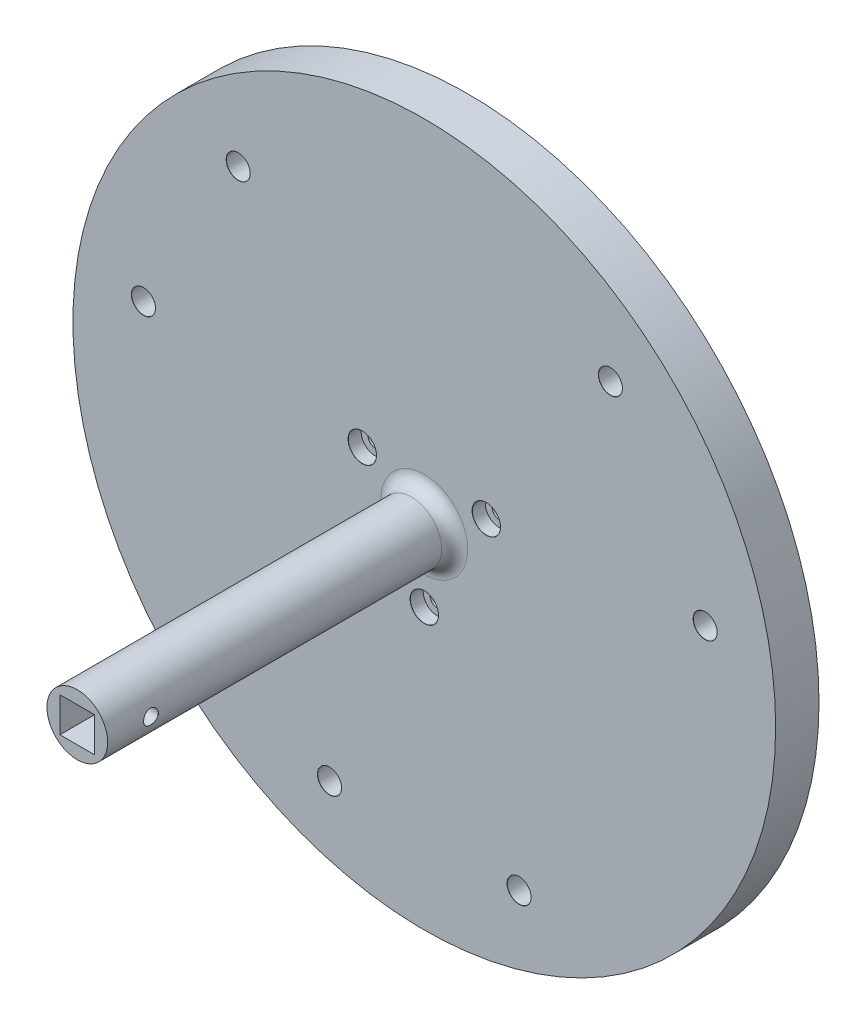
SolidWorks part; units mm, degrees
ref_plane "Front Plane" through (0, 0, 0) normal (0, 0, 1) x (1, 0, 0)
ref_plane "Top Plane" through (0, 0, 0) normal (0, 1, 0) x (1, 0, 0)
ref_plane "Right Plane" through (0, 0, 0) normal (1, 0, 0) x (0, 0, -1)
sketch "Sketch1" plane through (0, 0, 0) normal (0, 0, 1) x (1, 0, 0)
  circle A0 centre (0, 0) radius 81
  dimension "D1" = 162
extrude "Boss-Extrude1" add sketch "Sketch1" along normal blind 10
sketch "Sketch14" plane through (0, 0, 10) normal (0, 0, 1) x (1, 0, 0)
ref_axis "Axis2" through (0, 0, 38.9853) along (0, 0, -1)
sketch "Sketch2" plane through (0, 0, 10) normal (0, 0, 1) x (1, 0, 0)
  line L0 (0, 0) -> (0, -16.51) construction
  line L1 (-14.2981, 8.255) -> (0, 0) construction
  line L2 (0, 0) -> (14.2981, 8.255) construction
  circle A0 centre (0, 0) radius 16.51 construction
  point P7 (-14.2981, 8.255)
  point P8 (14.2981, 8.255)
  point P9 (0, -16.51)
  dimension "D1" = 16.51
  dimension "D2" = 120
  dimension "D3" = 120
sketch "Sketch5" plane through (0, 0, 10) normal (0, 0, 1) x (1, 0, 0)
  point P0 (-14.2981, 8.255)
  point P3 (14.2981, 8.255)
  point P6 (0, -16.51)
hole_wizard "CBORE for M3 SHCS1" positions "Sketch5" profile "Sketch4" counterbore size "M3" standard "ANSI Metric" end condition up to next
sketch "Sketch4" plane through (-14.2981, 8.255, 10) normal (1, 0, 0) x (0, -1, 0)
  line L0 (0, 0) -> (0, 10)
  line L1 (0, 10) -> (1.7, 10)
  line L3 (1.7, 10) -> (1.7, 3)
  line L4 (3.25, 3) -> (1.7, 3)
  line L5 (3.25, 3) -> (3.25, 0.025)
  line L6 (3.25, 0.025) -> (3.275, 0)
  line L7 (3.275, 0) -> (0, 0)
  line L8 (-3.25, 0.025) -> (-3.275, 0) construction
  line L11 (0, -6.35) -> (0, 107.95) construction
  dimension "Thru Hole Dia." = 3.4
  dimension "Thru Hole Depth" = 10
  dimension "C'Bore Dia." = 6.5
  dimension "C'Bore Depth" = 3
  dimension "Near C'Sink Dia." = 6.55
  dimension "Near C'Sink Angle" = 90
sketch "Sketch6" plane through (0, 0, 10) normal (0, 0, 1) x (1, 0, 0)
  circle A0 centre (0, 0) radius 7
  dimension "D1" = 14
extrude "Boss-Extrude2" add sketch "Sketch6" along normal blind 80
sketch "Sketch20" plane through (0, 0, 90) normal (0, 0, 1) x (1, 0, 0)
  line L1 (-4, 4) -> (4, 4)
  line L2 (-4, 4) -> (-4, -4)
  line L3 (-4, -4) -> (4, -4)
  line L4 (4, 4) -> (4, -4)
  line L5 (-4, 4) -> (4, -4) construction
  line L6 (-4, -4) -> (4, 4) construction
  point P0 (0, 0)
  dimension "D1" = 8
extrude "Cut-Extrude1" cut sketch "Sketch20" against normal blind 20
sketch "Sketch27" plane through (0, 0, 10) normal (0, 0, 1) x (1, 0, 0)
  line L0 (-21.85, -62.15) -> (21.85, -62.15) construction
  line L2 (0, 0) -> (0, -81) construction
  circle A0 centre (0, 0) radius 81 construction
  point P0 (-21.85, -62.15)
  point P2 (21.85, -62.15)
  point P17 (0, -62.15)
  dimension "D1" = 43.7
  dimension "D2" = 62.15
hole_wizard "M5 Clearance Hole3" positions "Sketch27" profile "Sketch26" hole size "M5" standard "ANSI Metric" end condition up to next
sketch "Sketch26" plane through (-21.85, -62.15, 10) normal (1, 0, 0) x (0, -1, 0)
  line L0 (0, 0) -> (0, 10)
  line L1 (0, 10) -> (2.75, 10)
  line L2 (2.75, 10) -> (2.75, 0.025)
  line L3 (2.75, 0.025) -> (2.775, 0)
  line L5 (2.775, 0) -> (0, 0)
  line L6 (-2.75, 0.025) -> (-2.775, 0) construction
  line L11 (0, -6.35) -> (0, 107.95) construction
  dimension "Thru Hole Dia." = 5.5
  dimension "Thru Hole Depth" = 10
  dimension "Near C'Sink Dia." = 5.55
  dimension "Near C'Sink Angle" = 90
pattern_circular "CirPattern1" count 3 over 360 about axis through (0, 0, 38.9853) along (0, 0, -1) of "M5 Clearance Hole3"
ref_plane "Plane1" through (7, 0, 0) normal (1, 0, 0) x (0, 0, -1)
sketch "Sketch34" plane through (7, 0, 0) normal (1, 0, 0) x (0, 0, -1)
  line L0 (-90, 7) -> (-90, -7) construction
  line L1 (-90, 7) -> (-90, -7) construction
  point P0 (-80, 0)
  point P10 (-90, 0)
  dimension "D1" = 10
hole_wizard "M3 Clearance Hole2" positions "Sketch34" profile "Sketch33" hole size "M3" standard "ANSI Metric" end condition through all
sketch "Sketch33" plane through (7, 0, 80) normal (0, 1, 0) x (0, 0, -1)
  line L0 (0, 0) -> (0, 88)
  line L1 (0, 88) -> (1.7, 88)
  line L2 (1.7, 88) -> (1.7, 0.025)
  line L3 (1.7, 0.025) -> (1.725, 0)
  line L5 (1.725, 0) -> (0, 0)
  line L6 (-1.7, 0.025) -> (-1.725, 0) construction
  line L11 (0, -6.35) -> (0, 107.95) construction
  dimension "Thru Hole Dia." = 3.4
  dimension "Thru Hole Depth" = 88
  dimension "Near C'Sink Dia." = 3.45
  dimension "Near C'Sink Angle" = 90
fillet "Fillet1" radius 3 1 edges at (7, 0, 10)
